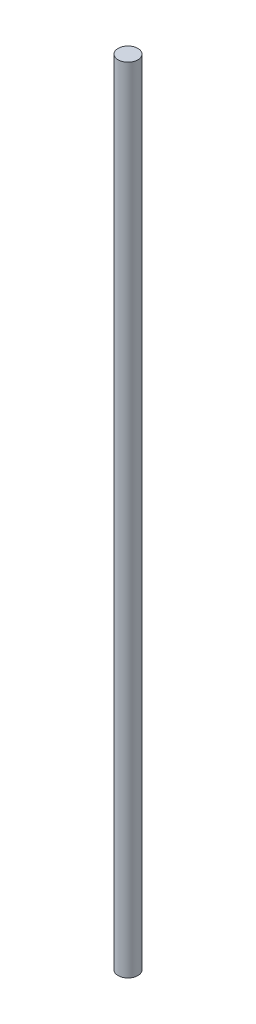
SolidWorks part; units mm, degrees
material "Hexcel AS4C (3000 Filaments)"
ref_plane "Front Plane" through (0, 0, 0) normal (0, 0, 1) x (1, 0, 0)
ref_plane "Top Plane" through (0, 0, 0) normal (0, 1, 0) x (1, 0, 0)
ref_plane "Right Plane" through (0, 0, 0) normal (1, 0, 0) x (0, 0, -1)
sketch "Sketch1" plane through (0, 0, 0) normal (0, 1, 0) x (1, 0, 0)
  circle A0 centre (0, 0) radius 6.25
  dimension "D1" = 12.5
extrude "Boss-Extrude1" add sketch "Sketch1" along normal blind 250 and the other way blind 250
ref_plane "Plane1" through (0, 185, 0) normal (0, 1, 0) x (1, 0, 0)
sketch "Sketch2" plane through (0, 185, 0) normal (0, 1, 0) x (1, 0, 0)
  point P0 (0, 0)
ref_plane "Plane2" through (0, -185, 0) normal (0, -1, 0) x (-1, 0, 0)
sketch "Sketch3" plane through (0, -185, 0) normal (0, -1, 0) x (-1, 0, 0)
  point P0 (0, 0)
